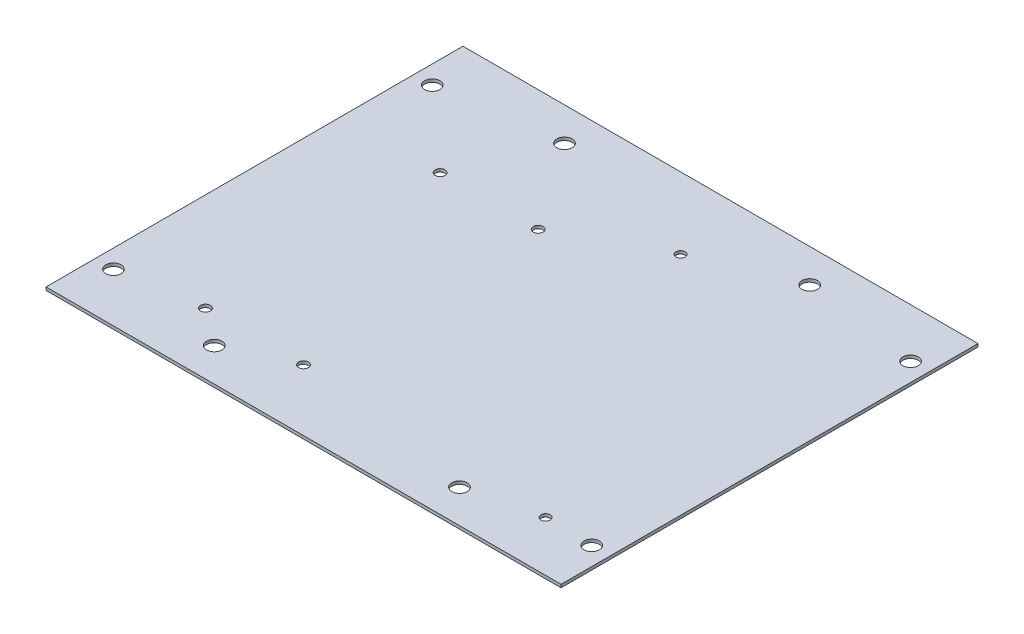
SolidWorks part; units mm, degrees
ref_plane "Front Plane" through (0, 0, 0) normal (0, 0, 1) x (1, 0, 0)
ref_plane "Top Plane" through (0, 0, 0) normal (0, 1, 0) x (1, 0, 0)
ref_plane "Right Plane" through (0, 0, 0) normal (1, 0, 0) x (0, 0, -1)
sketch "Sketch1" plane through (0, 0, 0) normal (0, 1, 0) x (1, 0, 0)
  line L1 (-133.35, -107.95) -> (133.35, -107.95)
  line L2 (-133.35, -107.95) -> (-133.35, 107.95)
  line L3 (-133.35, 107.95) -> (133.35, 107.95)
  line L4 (133.35, -107.95) -> (133.35, 107.95)
  line L5 (-133.35, -107.95) -> (133.35, 107.95) construction
  line L6 (-133.35, 107.95) -> (133.35, -107.95) construction
  point P0 (0, 0)
  dimension "D1" = 266.7
  dimension "D2" = 215.9
base flange "Base-Flange1" sketch "Sketch1" thickness 1.5748 reverse thickness direction no parameters "D1"=3
sketch "Sketch6" plane through (0, 0, 0) normal (0, 1, 0) x (1, 0, 0)
  line L0 (-133.35, 107.95) -> (-133.35, -107.95) construction
  line L1 (-133.35, -107.95) -> (133.35, -107.95) construction
  circle A0 centre (-123.825, -82.55) radius 3.9687
  dimension "D1" = 7.9375
  dimension "D2" = 9.525
  dimension "D3" = 25.4
extrude "Cut-Extrude1" cut sketch "Sketch6" against normal up to surface (1.5748 mm away) normal cut yes up to face at (0, -1.5748, 0)
sketch "Sketch7" plane through (0, 0, 0) normal (0, 1, 0) x (1, 0, 0)
  line L0 (-133.35, 107.95) -> (-133.35, -107.95) construction
  line L1 (-133.35, -107.95) -> (133.35, -107.95) construction
  circle A0 centre (-63.5, -90.678) radius 3.9687
  circle A1 centre (-123.825, -82.55) radius 3.9687 construction
  dimension "D1" = 69.85
  dimension "D2" = 17.272
extrude "Cut-Extrude2" cut sketch "Sketch7" against normal through all normal cut yes
mirror "Mirror1" about plane through (0, 0, 0) normal (1, 0, 0) of "Cut-Extrude2", "Cut-Extrude1"
mirror "Mirror2" about plane through (0, 0, 0) normal (0, 0, 1) of "Mirror1", "Cut-Extrude1", "Cut-Extrude2"
sketch "Sketch8" plane through (0, 0, 0) normal (0, 1, 0) x (1, 0, 0)
  line L0 (-133.35, 107.95) -> (-133.35, -107.95) construction
  line L1 (-133.35, -107.95) -> (133.35, -107.95) construction
  circle A0 centre (-82.55, -76.2) radius 2.54
  circle A1 centre (-31.75, -76.2) radius 2.54
  circle A2 centre (-82.55, 45.339) radius 2.54
  circle A3 centre (-31.75, 45.339) radius 2.54
  dimension "D5" = 5.08
  dimension "D1" = 50.8
  dimension "D2" = 121.539
  dimension "D3" = 50.8
  dimension "D4" = 31.75
extrude "Cut-Extrude3" cut sketch "Sketch8" against normal through all normal cut yes
sketch "Sketch9" plane through (0, 0, 0) normal (0, 1, 0) x (1, 0, 0)
  line L0 (-133.35, -107.95) -> (133.35, -107.95) construction
  line L1 (133.35, -107.95) -> (133.35, 107.95) construction
  line L2 (133.35, 107.95) -> (-133.35, 107.95) construction
  circle A0 centre (99.35, -81.95) radius 2.3813
  circle A1 centre (16.35, 70.95) radius 2.3812
  dimension "D3" = 4.7625
  dimension "D1" = 26
  dimension "D2" = 34
  dimension "D4" = 117
  dimension "D5" = 37
extrude "Cut-Extrude4" cut sketch "Sketch9" against normal through all normal cut yes
sketch "Bend-Lines1" [suppressed] plane through (0, 0, 0) normal (0, 1, 0) x (1, 0, 0)
sketch "Bounding-Box1" [suppressed] plane through (0, 0, 0) normal (0, 1, 0) x (1, 0, 0)
sheet metal parameters "Sheet-Metal1" thickness 1.5748 parameters "D1"=3
flat pattern "Flat-Pattern1" [suppressed]
sketch "Bend-Lines2" plane through (0, 0, 0) normal (0, 1, 0) x (1, 0, 0)
sketch3d "Bounding-Box2" [suppressed]
  line L0 (-127, 76.2, 0) -> (127, 76.2, 0) construction
  line L1 (-127, -76.2, 0) -> (127, -76.2, 0) construction
  line L2 (-127, 76.2, 0) -> (-127, -76.2, 0) construction
  line L3 (127, 76.2, 0) -> (127, -76.2, 0) construction
sheet metal parameters "Sheet-Metal2" thickness 1.5748 parameters "D1"=3
flat pattern "Flat-Pattern1"
sketch "Bend-Lines2" plane through (0, 0, 0) normal (0, 1, 0) x (1, 0, 0)
sketch3d "Bounding-Box2" [suppressed]
  line L0 (133.35, 107.95, 0) -> (-133.35, 107.95, 0) construction
  line L1 (133.35, -107.95, 0) -> (-133.35, -107.95, 0) construction
  line L2 (133.35, 107.95, 0) -> (133.35, -107.95, 0) construction
  line L3 (-133.35, 107.95, 0) -> (-133.35, -107.95, 0) construction
sheet metal parameters "Sheet-Metal3" thickness 1.5748 parameters "D1"=3
flat pattern "Flat-Pattern1"
sketch "Bend-Lines2" plane through (0, 0, 0) normal (0, 1, 0) x (1, 0, 0)
sketch3d "Bounding-Box2" [suppressed]
  line L0 (127, 76.2, 0) -> (-127, 76.2, 0) construction
  line L1 (127, -76.2, 0) -> (-127, -76.2, 0) construction
  line L2 (127, 76.2, 0) -> (127, -76.2, 0) construction
  line L3 (-127, 76.2, 0) -> (-127, -76.2, 0) construction
sheet metal parameters "Sheet-Metal4" thickness 1.5748 parameters "D1"=3
flat pattern "Flat-Pattern1"
sketch "Bend-Lines2" plane through (0, 0, 0) normal (0, 1, 0) x (1, 0, 0)
sketch3d "Bounding-Box2" [suppressed]
  line L0 (133.35, 107.95, 0) -> (-133.35, 107.95, 0) construction
  line L1 (133.35, -107.95, 0) -> (-133.35, -107.95, 0) construction
  line L2 (133.35, 107.95, 0) -> (133.35, -107.95, 0) construction
  line L3 (-133.35, 107.95, 0) -> (-133.35, -107.95, 0) construction
sheet metal parameters "Sheet-Metal5" thickness 1.5748 parameters "D1"=3
flat pattern "Flat-Pattern1"
sketch "Bend-Lines2" plane through (0, 0, 0) normal (0, 1, 0) x (1, 0, 0)
sketch3d "Bounding-Box2" [suppressed]
  line L0 (133.35, 107.95, 0) -> (-133.35, 107.95, 0) construction
  line L1 (133.35, -107.95, 0) -> (-133.35, -107.95, 0) construction
  line L2 (133.35, 107.95, 0) -> (133.35, -107.95, 0) construction
  line L3 (-133.35, 107.95, 0) -> (-133.35, -107.95, 0) construction
sheet metal parameters "Sheet-Metal6" thickness 1.5748 parameters "D1"=3
flat pattern "Flat-Pattern1"
sketch "Bend-Lines2" plane through (0, 0, 0) normal (0, 1, 0) x (1, 0, 0)
sketch3d "Bounding-Box2" [suppressed]
  line L0 (133.35, 107.95, 0) -> (-133.35, 107.95, 0) construction
  line L1 (133.35, -107.95, 0) -> (-133.35, -107.95, 0) construction
  line L2 (133.35, 107.95, 0) -> (133.35, -107.95, 0) construction
  line L3 (-133.35, 107.95, 0) -> (-133.35, -107.95, 0) construction
sheet metal parameters "Sheet-Metal7" thickness 1.5748 parameters "D1"=3
flat pattern "Flat-Pattern1"
sketch "Bend-Lines2" plane through (0, 0, 0) normal (0, 1, 0) x (1, 0, 0)
sketch3d "Bounding-Box2" [suppressed]
  line L0 (133.35, 107.95, 0) -> (-133.35, 107.95, 0) construction
  line L1 (133.35, -107.95, 0) -> (-133.35, -107.95, 0) construction
  line L2 (133.35, 107.95, 0) -> (133.35, -107.95, 0) construction
  line L3 (-133.35, 107.95, 0) -> (-133.35, -107.95, 0) construction
